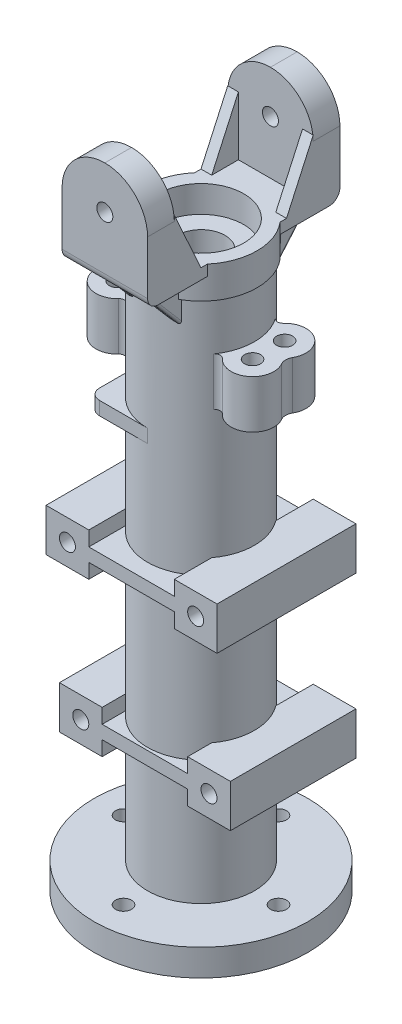
SolidWorks part; units mm, degrees
material "ABS"
ref_plane "Front Plane" through (0, 0, 0) normal (0, 0, 1) x (1, 0, 0)
ref_plane "Top Plane" through (0, 0, 0) normal (0, 1, 0) x (1, 0, 0)
ref_plane "Right Plane" through (0, 0, 0) normal (1, 0, 0) x (0, 0, -1)
sketch "Sketch1" plane through (0, 0, 0) normal (0, 1, 0) x (1, 0, 0)
  circle A0 centre (0, 0) radius 10
  dimension "D1" = 20
extrude "Boss-Extrude1" add sketch "Sketch1" along normal blind 111
ref_plane "Plane1" through (0, 2, 0) normal (0, -1, 0) x (-1, 0, 0)
sketch "Sketch2" plane through (0, 2, 0) normal (0, -1, 0) x (-1, 0, 0)
  circle A0 centre (0, 0) radius 20
  dimension "D1" = 40
extrude "Boss-Extrude2" add sketch "Sketch2" against normal blind 5
sketch "Sketch3" plane through (0, 2, 0) normal (0, -1, 0) x (1, 0, 0)
  circle A1 centre (0, 0) radius 10
  circle A2 centre (0, 0) radius 19
  circle A3 centre (0, 0) radius 19
  dimension "D1" = 1
extrude "Cut-Extrude1" cut sketch "Sketch3" against normal blind 2
sketch "Sketch4" plane through (0, 4, 0) normal (0, -1, 0) x (1, 0, 0)
  line L0 (0, 14.5) -> (0, 0) construction
  circle A0 centre (0, 14.5) radius 1.5
  circle A1 centre (0, 0) radius 20 construction
  circle A2 centre (14.5, 0) radius 1.5
  circle A3 centre (0, -14.5) radius 1.5
  circle A4 centre (-14.5, 0) radius 1.5
  point P15 (0, 0)
  dimension "D1" = 3
  dimension "D2" = 14.5
  dimension "D3" = 4
extrude "Cut-Extrude2" cut sketch "Sketch4" against normal through all
sketch "Sketch5" plane through (0, 0, 0) normal (0, 0, 1) x (1, 0, 0)
  line L0 (20, 7) -> (-20, 7) construction
  line L1 (-16, 25) -> (16, 25)
  line L2 (-16, 25) -> (-16, 33)
  line L3 (-16, 33) -> (16, 33)
  line L4 (16, 25) -> (16, 33)
  line L5 (-8, 33) -> (-8, 25)
  line L6 (0, 25) -> (0, 33) construction
  line L7 (8, 33) -> (8, 25)
  line L9 (-8, 30.25) -> (8, 30.25)
  line L10 (-8, 30.25) -> (-8, 27.75)
  line L11 (-8, 27.75) -> (8, 27.75)
  line L12 (8, 30.25) -> (8, 27.75)
  circle A0 centre (-12, 29) radius 1.5
  circle A1 centre (12, 29) radius 1.5
  point P21 (-8, 29)
  dimension "D5" = 3
  dimension "D6" = 4
  dimension "D8" = 4
  dimension "D1" = 18
  dimension "D2" = 8
  dimension "D3" = 32
  dimension "D4" = 16
  dimension "D7" = 8
  dimension "D9" = 2.5
  dimension "D10" = 1.25
extrude "Boss-Extrude3" add sketch "Sketch5" along normal mid plane 22 contours L5 L3 L2 L1 A0 | L11 L6 L9 L5 | L3 L7 L1 L4 A1 | L6 L11 L7 L9 region at (-15.8869, 29, 0) region at (-4, 29, 0) region at (8.1131, 26.375, 0) region at (4, 29, 0)
sketch "Sketch6" plane through (0, 0, 11) normal (0, 0, 1) x (1, 0, 0)
  line L0 (-8, 60.25) -> (-8, 63)
  line L1 (-8, 63) -> (-16, 63)
  line L2 (-16, 63) -> (-16, 55)
  line L3 (-16, 55) -> (-8, 55)
  line L4 (-8, 55) -> (-8, 57.75)
  line L5 (-8, 57.75) -> (8, 57.75)
  line L6 (8, 57.75) -> (8, 55)
  line L7 (8, 55) -> (16, 55)
  line L8 (16, 55) -> (16, 63)
  line L9 (16, 63) -> (8, 63)
  line L10 (8, 63) -> (8, 60.25)
  line L11 (8, 60.25) -> (-8, 60.25)
  line L24 (-8, 30.25) -> (-8, 33)
  line L25 (-8, 33) -> (-16, 33)
  line L26 (-16, 33) -> (-16, 25)
  line L27 (-16, 25) -> (-8, 25)
  line L28 (-8, 25) -> (-8, 27.75)
  line L29 (-8, 27.75) -> (8, 27.75)
  line L30 (8, 27.75) -> (8, 25)
  line L31 (8, 25) -> (16, 25)
  line L32 (16, 25) -> (16, 33)
  line L33 (16, 33) -> (8, 33)
  line L34 (8, 33) -> (8, 30.25)
  line L35 (8, 30.25) -> (-8, 30.25)
  line L36 (-8, 30.25) -> (-8, 33)
  line L37 (-8, 33) -> (-16, 33)
  line L38 (-16, 33) -> (-16, 25)
  line L39 (-16, 25) -> (-8, 25)
  line L40 (-8, 25) -> (-8, 27.75)
  line L41 (-8, 27.75) -> (8, 27.75)
  line L42 (8, 27.75) -> (8, 25)
  line L43 (8, 25) -> (16, 25)
  line L44 (16, 25) -> (16, 33)
  line L45 (16, 33) -> (8, 33)
  line L46 (8, 33) -> (8, 30.25)
  line L47 (8, 30.25) -> (-8, 30.25)
  circle A0 centre (-12, 59) radius 1.5
  circle A1 centre (12, 59) radius 1.5
  circle A2 centre (-12, 29) radius 1.5
  circle A3 centre (-12, 29) radius 1.5
  circle A5 centre (12, 29) radius 1.5
  circle A6 centre (12, 29) radius 1.5
  point P31 (-8, 56.375)
  circle M15 centre (-12, 29) radius 1.5
  line M16 (-8, 30.25) -> (-8, 33)
  line M17 (-8, 33) -> (-16, 33)
  line M18 (-16, 33) -> (-16, 25)
  line M19 (-16, 25) -> (-8, 25)
  line M20 (-8, 25) -> (-8, 27.75)
  line M21 (-8, 27.75) -> (8, 27.75)
  line M22 (8, 27.75) -> (8, 25)
  line M23 (8, 25) -> (16, 25)
  line M24 (16, 25) -> (16, 33)
  line M25 (16, 33) -> (8, 33)
  line M26 (8, 33) -> (8, 30.25)
  line M27 (8, 30.25) -> (-8, 30.25)
  circle M28 centre (12, 29) radius 1.5
  dimension "D10" = 4
  dimension "D11" = 4
  dimension "D12" = 4
  dimension "D13" = 4
  dimension "D20" = 3
  dimension "D21" = 3
  dimension "D4" = 32
  dimension "D5" = 8
  dimension "D6" = 8
  dimension "D7" = 8
  dimension "D8" = 8
  dimension "D9" = 16
  dimension "D14" = 2.75
  dimension "D15" = 2.5
  dimension "D16" = 0
  dimension "D17" = 2.75
  dimension "D18" = 0
  dimension "D19" = 22
  dimension "D1" = 0
  dimension "D2" = 0
  dimension "D3" = 0
extrude "Boss-Extrude4" add sketch "Sketch6" along normal blind 3 contours M27 M16 M17 M18 M19 M20 M21 M22 M23 M24 M25 M26 M28 M15 region at (0, 29, 11)
sketch "Sketch7" plane through (0, 0, 0) normal (1, 0, 0) x (0, 0, -1)
  line L0 (0, 0) -> (0, 111) construction
  line L1 (10, 111) -> (-10, 111) construction
  line L2 (-10, 111) -> (-10, 30.25) construction
  line L3 (-10, 82) -> (10, 82)
  line L4 (-10, 82) -> (-10, 79.5)
  line L5 (-10, 79.5) -> (10, 79.5)
  line L6 (10, 82) -> (10, 79.5)
  line L7 (10, 30.25) -> (10, 111) construction
  dimension "D1" = 2.5
  dimension "D2" = 31.5
extrude "Boss-Extrude5" add sketch "Sketch7" against normal blind 11
ref_plane "Plane2" through (0, 87, 0) normal (0, 1, 0) x (1, 0, 0)
sketch "Sketch8" plane through (0, 87, 0) normal (0, 1, 0) x (1, 0, 0)
  line L0 (0, 0) -> (20, 0) construction
  line L1 (0, 0) -> (0, 20) construction
  line L2 (0, 0) -> (12.6491, 3) construction
  line L3 (12.6491, -3) -> (12.6491, 3) construction
  circle A0 centre (0, 0) radius 20 construction
  circle A1 centre (12.6491, 3) radius 1.5
  circle A2 centre (12.6491, 3) radius 4
  circle A4 centre (12.6491, -3) radius 1.5
  circle A5 centre (12.6491, -3) radius 4
  circle A7 centre (-12.6491, -3) radius 1.5
  circle A8 centre (0, 0) radius 10
  circle A9 centre (0, 0) radius 10
  circle A10 centre (-12.6491, 3) radius 1.5
  circle A11 centre (-12.6491, -3) radius 4
  circle A12 centre (-12.6491, 3) radius 4
  dimension "D1" = 3
  dimension "D2" = 8
  dimension "D3" = 13
  dimension "D4" = 6
  dimension "D5" = 0
extrude "Boss-Extrude6" add sketch "Sketch8" along normal blind 9 contours A12 A11 A9 A10 | A11 A12 A9 A7 | A9 A2 A5 A1 | A9 A5 A2 A4 | A5 A2 | A12 A11 region at (16.1999, 87, -1.3971) region at (16.1999, 87, 1.3971) region at (12.6491, 87, 0) region at (-9.8314, 87, -2.3317) region at (-12.6491, 87, 1.1042) region at (-12.6491, 87, 0)
fillet "Fillet1" radius 1 4 edges at (8.9362, 91.5, -4.4882) (8.9362, 91.5, 4.4882) (-8.9362, 91.5, 4.4882) (-8.9362, 91.5, -4.4882)
fillet "Fillet2" radius 2 2 edges at (-15.2949, 91.5, 0) (15.2949, 91.5, 0)
sketch "Sketch9" plane through (0, 111, 0) normal (0, 1, 0) x (1, 0, 0)
  circle A0 centre (0, 0) radius 10.5
  dimension "D1" = 21
extrude "Boss-Extrude7" add sketch "Sketch9" against normal blind 6
fillet "Fillet3" radius 2 2 edges at (-11, 80.75, 10) (-11, 80.75, -10)
sketch "Sketch10" plane through (0, 0, 0) normal (1, 0, 0) x (0, 0, -1)
  line L0 (0, 0) -> (0, 89.8082) construction
  line L1 (10.5, 111) -> (-10.5, 111) construction
  line L2 (-18, 129) -> (-13, 129)
  line L3 (-18, 129) -> (-18, 109)
  line L4 (-18, 109) -> (-13, 109)
  line L5 (-13, 129) -> (-13, 109)
  line L14 (18, 109) -> (13, 109)
  line L15 (13, 129) -> (13, 109)
  line L16 (18, 129) -> (13, 129)
  line L17 (18, 129) -> (18, 109)
  line L19 (-13, 109) -> (13, 109)
  line L20 (-13, 109) -> (-13, 111)
  line L21 (-13, 111) -> (13, 111)
  line L22 (13, 109) -> (13, 111)
  dimension "D1" = 18
  dimension "D2" = 5
  dimension "D3" = 20
  dimension "D4" = 18
  dimension "D5" = 2
extrude "Boss-Extrude8" add sketch "Sketch10" along normal mid plane 16 contours L0 L19 L15 L21 | L19 L0 L21 L5 | L5 L2 L3 L4 | L17 L16 L15 L14 region at (0, 119, 15.5) region at (0, 110, 0) region at (0, 119, -15.5)
fillet "Fillet5" radius 8 4 edges at (-8, 129, 15.5) (8, 129, 15.5) (8, 129, -15.5) (-8, 129, -15.5)
sketch "Sketch11" plane through (0, 0, -18) normal (0, 0, -1) x (-1, 0, 0)
  circle A0 centre (0, 121) radius 1.5
extrude "Cut-Extrude3" cut sketch "Sketch11" against normal through all
ref_plane "Plane3" through (8, 0, 0) normal (1, 0, 0) x (0, 0, -1)
sketch "Sketch12" plane through (8, 0, 0) normal (1, 0, 0) x (0, 0, -1)
  line L6 (-13, 111) -> (-8, 111)
  line L7 (6.8007, 111) -> (-6.8007, 111) construction
  line L8 (-8, 111) -> (-13, 122)
  line L9 (-13, 121) -> (-13, 129) construction
  line L10 (-13, 122) -> (-13, 111)
  dimension "D1" = 11
  dimension "D2" = 5
extrude "Boss-Extrude9" add sketch "Sketch12" against normal blind 2
mirror "Mirror1" about plane through (0, 0, 0) normal (1, 0, 0) of "Boss-Extrude9"
mirror "Mirror2" about plane through (0, 0, 0) normal (0, 0, 1) of "Mirror1"
sketch "Sketch13" plane through (0, 111, 0) normal (0, 1, 0) x (1, 0, 0)
  circle A0 centre (0, 0) radius 8
  dimension "D1" = 16
extrude "Cut-Extrude4" cut sketch "Sketch13" against normal blind 5
sketch "Sketch14" plane through (0, 0, 0) normal (0, -1, 0) x (1, 0, 0)
  circle A0 centre (0, 0) radius 8
  dimension "D1" = 16
extrude "Cut-Extrude5" cut sketch "Sketch14" against normal blind 5
sketch "Sketch15" plane through (0, 5, 0) normal (0, -1, 0) x (1, 0, 0)
  circle A0 centre (0, 0) radius 7
  dimension "D1" = 14
extrude "Cut-Extrude6" cut sketch "Sketch15" against normal blind 51
sketch "Sketch16" plane through (0, 106, 0) normal (0, 1, 0) x (1, 0, 0)
  circle A0 centre (0, 0) radius 4.5
extrude "Cut-Extrude7" cut sketch "Sketch16" against normal through all
ref_plane "Plane4" through (5, 0, 0) normal (1, 0, 0) x (0, 0, -1)
sketch "Sketch18" plane through (5, 0, 0) normal (1, 0, 0) x (0, 0, -1)
  line L0 (-16, 109) -> (-10, 102)
  line L1 (-18, 109) -> (-6.8007, 109) construction
  line L2 (-10, 105) -> (-10, 82) construction
  line L3 (-10, 102) -> (-10, 109)
  line L4 (-10.5, 109) -> (-6.8007, 109) construction
  line L5 (-10, 109) -> (-16, 109)
  line L6 (-10, 102) -> (-8.4976, 100.2472)
  line L7 (-8.4976, 100.2472) -> (-8.6504, 109)
  line L8 (-8.6504, 109) -> (-10, 109)
  dimension "D1" = 6
  dimension "D2" = 7
  dimension "D3" = 1
extrude "Boss-Extrude10" add sketch "Sketch18" against normal blind 2 contours L3 L5 L0 | L7 L8 L3 L6 region at (5, 106.6667, 12) region at (5, 104.9834, 9.2612)
mirror "Mirror3" about plane through (0, 0, 0) normal (1, 0, 0) of "Boss-Extrude10"
mirror "Mirror4" about plane through (0, 0, 0) normal (0, 0, 1) of "Mirror3"
fillet "Fillet6" radius 0.5 2 edges at (-3, 105.2313, 12.7697) (-5, 104.7185, 12.3301)
fillet "Fillet7" radius 0.5 2 edges at (5, 104.7185, 12.3301) (3, 105.2313, 12.7697)
fillet "Fillet8" radius 0.5 2 edges at (3, 105.2313, -12.7697) (5, 104.7185, -12.3301)
fillet "Fillet9" radius 0.5 2 edges at (-3, 105.2313, -12.7697) (-5, 104.7185, -12.3301)
fillet "Fillet10" radius 2 2 edges at (0, 109, 18) (0, 109, -18)
extrude "Boss-Extrude11" add sketch "Sketch6<3>" along normal mid plane 22 from surface contours L10 L11 L0 L1 L2 L3 L4 L5 L6 L7 L8 L9 A1 A0 region at (0, 59, 11) starting at plane "Front Plane"
sketch "Sketch6<3>" plane through (0, 0, 11) normal (0, 0, 1) x (1, 0, 0) same geometry as "Sketch6"
sketch "Sketch19" plane through (0, 0, 14) normal (0, 0, 1) x (1, 0, 0)
  line L24 (8, 30.25) -> (-8, 30.25)
  line L25 (-8, 30.25) -> (-8, 33)
  line L26 (-8, 33) -> (-16, 33)
  line L27 (-16, 33) -> (-16, 25)
  line L28 (-16, 25) -> (-8, 25)
  line L29 (-8, 25) -> (-8, 27.75)
  line L30 (-8, 27.75) -> (8, 27.75)
  line L31 (8, 27.75) -> (8, 25)
  line L32 (8, 25) -> (16, 25)
  line L33 (16, 25) -> (16, 33)
  line L34 (16, 33) -> (8, 33)
  line L35 (8, 33) -> (8, 30.25)
  line L36 (8, 30.25) -> (-8, 30.25)
  line L37 (-8, 30.25) -> (-8, 33)
  line L38 (-8, 33) -> (-16, 33)
  line L39 (-16, 33) -> (-16, 25)
  line L40 (-16, 25) -> (-8, 25)
  line L41 (-8, 25) -> (-8, 27.75)
  line L42 (-8, 27.75) -> (8, 27.75)
  line L43 (8, 27.75) -> (8, 25)
  line L44 (8, 25) -> (16, 25)
  line L45 (16, 25) -> (16, 33)
  line L46 (16, 33) -> (8, 33)
  line L47 (8, 33) -> (8, 30.25)
  circle A2 centre (-12, 29) radius 1.5
  circle A3 centre (-12, 29) radius 1.5
  circle A5 centre (12, 29) radius 1.5
  circle A6 centre (12, 29) radius 1.5
  dimension "D1" = 0
  dimension "D2" = 0
  dimension "D3" = 0
extrude "Cut-Extrude8" cut sketch "Sketch19" against normal blind 3.5
sketch "Sketch20" plane through (0, 0, -11) normal (0, 0, -1) x (-1, 0, 0)
  line L24 (-16, 55) -> (-8, 55)
  line L25 (-8, 55) -> (-8, 57.75)
  line L26 (-8, 57.75) -> (8, 57.75)
  line L27 (8, 57.75) -> (8, 55)
  line L28 (8, 55) -> (16, 55)
  line L29 (16, 55) -> (16, 63)
  line L30 (16, 63) -> (8, 63)
  line L31 (8, 63) -> (8, 60.25)
  line L32 (8, 60.25) -> (-8, 60.25)
  line L33 (-8, 60.25) -> (-8, 63)
  line L34 (-8, 63) -> (-16, 63)
  line L35 (-16, 63) -> (-16, 55)
  line L36 (-16, 55) -> (-8, 55)
  line L37 (-8, 55) -> (-8, 57.75)
  line L38 (-8, 57.75) -> (8, 57.75)
  line L39 (8, 57.75) -> (8, 55)
  line L40 (8, 55) -> (16, 55)
  line L41 (16, 55) -> (16, 63)
  line L42 (16, 63) -> (8, 63)
  line L43 (8, 63) -> (8, 60.25)
  line L44 (8, 60.25) -> (-8, 60.25)
  line L45 (-8, 60.25) -> (-8, 63)
  line L46 (-8, 63) -> (-16, 63)
  line L47 (-16, 63) -> (-16, 55)
  line L60 (8, 33) -> (8, 30.25)
  line L61 (8, 30.25) -> (-8, 30.25)
  line L62 (-8, 30.25) -> (-8, 33)
  line L63 (-8, 33) -> (-16, 33)
  line L64 (-16, 33) -> (-16, 25)
  line L65 (-16, 25) -> (-8, 25)
  line L66 (-8, 25) -> (-8, 27.75)
  line L67 (-8, 27.75) -> (8, 27.75)
  line L68 (8, 27.75) -> (8, 25)
  line L69 (8, 25) -> (16, 25)
  line L70 (16, 25) -> (16, 33)
  line L71 (16, 33) -> (8, 33)
  line L72 (8, 33) -> (8, 30.25)
  line L73 (8, 30.25) -> (-8, 30.25)
  line L74 (-8, 30.25) -> (-8, 33)
  line L75 (-8, 33) -> (-16, 33)
  line L76 (-16, 33) -> (-16, 25)
  line L77 (-16, 25) -> (-8, 25)
  line L78 (-8, 25) -> (-8, 27.75)
  line L79 (-8, 27.75) -> (8, 27.75)
  line L80 (8, 27.75) -> (8, 25)
  line L81 (8, 25) -> (16, 25)
  line L82 (16, 25) -> (16, 33)
  line L83 (16, 33) -> (8, 33)
  circle A2 centre (-12, 59) radius 1.5
  circle A3 centre (-12, 59) radius 1.5
  circle A5 centre (12, 59) radius 1.5
  circle A6 centre (12, 59) radius 1.5
  circle A8 centre (-12, 29) radius 1.5
  circle A9 centre (-12, 29) radius 1.5
  circle A11 centre (12, 29) radius 1.5
  circle A12 centre (12, 29) radius 1.5
  dimension "D1" = 0
  dimension "D2" = 0
  dimension "D3" = 0
  dimension "D4" = 0
  dimension "D5" = 0
  dimension "D6" = 0
extrude "Boss-Extrude12" add sketch "Sketch20" along normal blind 2
sketch "Sketch21" plane through (0, 0, 11) normal (0, 0, 1) x (1, 0, 0)
  line L24 (8, 55) -> (16, 55)
  line L25 (16, 55) -> (16, 63)
  line L26 (16, 63) -> (8, 63)
  line L27 (8, 63) -> (8, 60.25)
  line L28 (8, 60.25) -> (-8, 60.25)
  line L29 (-8, 60.25) -> (-8, 63)
  line L30 (-8, 63) -> (-16, 63)
  line L31 (-16, 63) -> (-16, 55)
  line L32 (-16, 55) -> (-8, 55)
  line L33 (-8, 55) -> (-8, 57.75)
  line L34 (-8, 57.75) -> (8, 57.75)
  line L35 (8, 57.75) -> (8, 55)
  line L36 (8, 55) -> (16, 55)
  line L37 (16, 55) -> (16, 63)
  line L38 (16, 63) -> (8, 63)
  line L39 (8, 63) -> (8, 60.25)
  line L40 (8, 60.25) -> (-8, 60.25)
  line L41 (-8, 60.25) -> (-8, 63)
  line L42 (-8, 63) -> (-16, 63)
  line L43 (-16, 63) -> (-16, 55)
  line L44 (-16, 55) -> (-8, 55)
  line L45 (-8, 55) -> (-8, 57.75)
  line L46 (-8, 57.75) -> (8, 57.75)
  line L47 (8, 57.75) -> (8, 55)
  circle A2 centre (12, 59) radius 1.5
  circle A3 centre (12, 59) radius 1.5
  circle A5 centre (-12, 59) radius 1.5
  circle A6 centre (-12, 59) radius 1.5
  dimension "D1" = 0
  dimension "D2" = 0
  dimension "D3" = 0
extrude "Boss-Extrude13" add sketch "Sketch21" along normal blind 2
